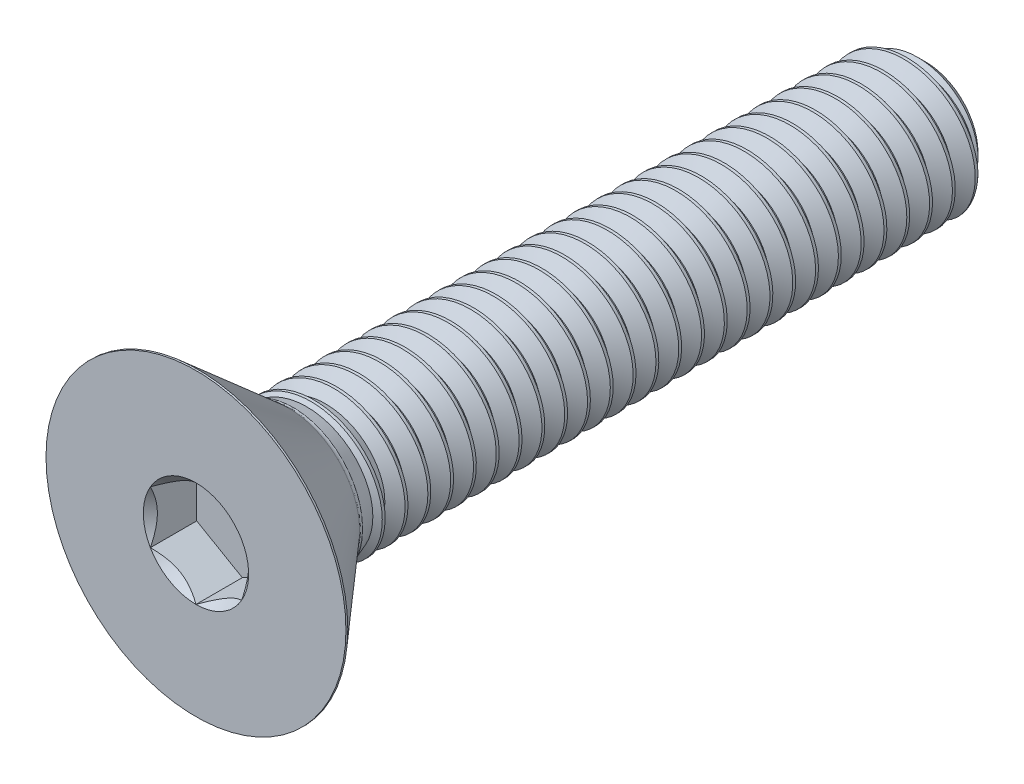
SolidWorks part; units mm, degrees
ref_plane "Front Plane" through (0, 0, 0) normal (0, 0, 1) x (1, 0, 0)
ref_plane "Top Plane" through (0, 0, 0) normal (0, 1, 0) x (1, 0, 0)
ref_plane "Right Plane" through (0, 0, 0) normal (1, 0, 0) x (0, 0, -1)
sketch "Sketch1" plane through (0, 0, 0) normal (1, 0, 0) x (0, 0, -1)
  line L0 (-12.7, 0) -> (12.7, 0) construction
  line L1 (-12.7, 0) -> (-12.7, 5.2197)
  line L2 (-12.7, 5.2197) -> (-12.6355, 5.2197)
  line L3 (-12.6355, 5.2197) -> (-9.4742, 2.4716)
  line L4 (-12.6355, -5.2197) -> (-9.4742, -2.4716)
  line L5 (12.7, 0) -> (12.7, 2.413)
  line L6 (12.7, 2.413) -> (-9.4742, 2.413)
  line L7 (12.1047, 2.413) -> (12.7, 1.8177)
  line L8 (12.6504, 2.4989) -> (13.0473, 1.8115) construction
  line L9 (13.0473, 1.8115) -> (13.4441, 2.4989) construction
  line L10 (13.4441, 2.4989) -> (12.6504, 2.4989) construction
  line L11 (12.6752, 2.456) -> (13.4193, 2.456)
  line L12 (13.4193, 2.456) -> (13.0969, 1.8974)
  line L13 (13.0969, 1.8974) -> (12.9977, 1.8974)
  line L14 (12.9977, 1.8974) -> (12.6752, 2.456)
  line L15 (13.0473, 1.8974) -> (13.0473, 1.8115) construction
  line L16 (12.7, 2.413) -> (13.3945, 2.413) construction
  line L17 (13.0473, 2.4989) -> (13.0473, 2.413) construction
  line L18 (12.7, -2.413) -> (-9.4742, -2.413)
  arc A0 (-9.4742, 2.4716) -> (-9.3174, 2.413) centre (-9.3174, 2.6521) ccw
  point P2 (0, 0)
  point P23 (-11.0871, 0)
  point P27 (13.0473, 2.456)
  point P30 (11.5094, -2.413)
  point P31 (-6.7075, 2.413)
  point P32 (10.0901, 2.413)
  point P33 (-9.4742, 5.2197)
  point P34 (-12.6355, -5.2197)
  point P37 (-6.0551, 2.413)
  dimension "Length" = 25.4
  dimension "Head Height" = 3.2258
  dimension "Head Diameter" = 10.4394
  dimension "Countersink Angle" = 82
  dimension "Screw Size Decimal Equivalent" = 4.826
  dimension "Pitch" = 0.7937
  dimension "D4" = 0.0992
  dimension "D3" = 45
  dimension "D5" = 0.5953
  dimension "D6" = 1.6129
  dimension "D1" = 1.1906
  dimension "D7" = 2.6098
  dimension "D8" = 2.6098
  dimension "D9" = 3.2623
  dimension "D2" = 0.0645
sketch "Sketch2" plane through (0, 0, 0) normal (0, 0, 1) x (1, 0, 0)
  line L1 (0, 1.8331) -> (-1.5875, 0.9165)
  line L2 (-1.5875, 0.9165) -> (-1.5875, -0.9165)
  line L3 (-1.5875, -0.9165) -> (0, -1.8331)
  line L4 (0, -1.8331) -> (1.5875, -0.9165)
  line L5 (1.5875, -0.9165) -> (1.5875, 0.9165)
  line L6 (1.5875, 0.9165) -> (0, 1.8331)
  circle A0 centre (0, 0) radius 1.5875 construction
  dimension "Drive Size" = 3.175
sketch "Sketch3" plane through (0, 0, 0) normal (1, 0, 0) x (0, 0, -1)
  line L0 (-12.6355, 5.2197) -> (-9.4742, 2.4716) construction
  line L1 (-12.7, 0) -> (-12.7, 5.2197) construction
  line L2 (-12.6355, 5.2197) -> (-9.4742, 2.4716)
  line L3 (-12.7, 0) -> (-12.7, 5.2197)
  line L4 (-12.7, 5.2197) -> (-12.6355, 5.2197) construction
  line L5 (-12.7, 5.2197) -> (-12.6355, 5.2197)
  line L6 (-9.3174, 2.413) -> (12.1047, 2.413)
  line L7 (12.1047, 2.413) -> (12.7, 1.8177)
  line L8 (12.7, 1.8177) -> (12.7, 0)
  line L9 (12.7, 0) -> (-12.7, 0)
  arc A0 (-9.4742, 2.4716) -> (-9.3174, 2.413) centre (-9.3174, 2.6521) ccw construction
  arc A1 (-9.4742, 2.4716) -> (-9.3174, 2.413) centre (-9.3174, 2.6521) ccw
revolve "Revolve1" add sketch "Sketch3" angle 360 about L9
sketch "Sketch4" plane through (0, 0, 12.7) normal (0, 0, 1) x (1, 0, 0)
  line L0 (1.5875, -0.9165) -> (1.5875, 0.9165) construction
  line L1 (0, -1.8331) -> (1.5875, -0.9165) construction
  line L2 (-1.5875, -0.9165) -> (0, -1.8331) construction
  line L3 (-1.5875, 0.9165) -> (-1.5875, -0.9165) construction
  line L4 (0, 1.8331) -> (-1.5875, 0.9165) construction
  line L5 (1.5875, 0.9165) -> (0, 1.8331) construction
  line L6 (1.5875, -0.9165) -> (1.5875, 0.9165)
  line L7 (0, -1.8331) -> (1.5875, -0.9165)
  line L8 (-1.5875, -0.9165) -> (0, -1.8331)
  line L9 (-1.5875, 0.9165) -> (-1.5875, -0.9165)
  line L10 (0, 1.8331) -> (-1.5875, 0.9165)
  line L11 (1.5875, 0.9165) -> (0, 1.8331)
sketch "Sketch5" plane through (0, 0, 12.7) normal (0, 0, 1) x (1, 0, 0)
  circle A0 centre (0, 0) radius 1.8331
extrude "Cut-Extrude1" cut sketch "Sketch5" against normal up to vertex (1.6129 mm away) draft 45 up to point (0, 0, 11.0871)
extrude "Cut-Extrude2" cut sketch "Sketch4" against normal up to vertex (1.6129 mm away) up to point (0, 0, 11.0871)
ref_plane "Plane1" through (0, 0, 9.3174) normal (0, 0, 1) x (1, 0, 0)
split "Split1" trim tools "Plane1" bodies to split 111 resulting bodies 105 106
sketch "Sketch6" plane through (0, 0, -12.7) normal (0, 0, -1) x (-1, 0, 0)
  circle A0 centre (0, 0) radius 2.413 construction
  circle A1 centre (0, 0) radius 2.413
curve "Helix/Spiral1" pitch 0.7937 height 25.4 turns 32
sketch "Sketch7" plane through (0, 0, 0) normal (1, 0, 0) x (0, 0, -1)
  line L0 (12.6752, 2.456) -> (13.4193, 2.456) construction
  line L1 (12.9977, 1.8974) -> (12.6752, 2.456) construction
  line L2 (13.0969, 1.8974) -> (12.9977, 1.8974) construction
  line L3 (13.4193, 2.456) -> (13.0969, 1.8974) construction
  line L4 (12.6752, 2.456) -> (13.4193, 2.456)
  line L5 (12.9977, 1.8974) -> (12.6752, 2.456)
  line L6 (13.0969, 1.8974) -> (12.9977, 1.8974)
  line L7 (13.4193, 2.456) -> (13.0969, 1.8974)
sweep "Cut-Sweep1" cut profiles "Sketch7" path "Helix/Spiral1"
sketch "Sketch8" plane through (0, 0, 9.3174) normal (0, 0, 1) x (1, 0, 0)
  circle A0 centre (0, 0) radius 2.413
extrude "Boss-Extrude1" add sketch "Sketch8" against normal up to next (22.0174 mm away) draft 20
equation "\"D4@Sketch1\" = \"Pitch@Sketch1\" / 8"
equation "\"D5@Sketch1\"=\"Pitch@Sketch1\"*0.75"
equation "\"D4@Helix/Spiral1\"=\"Pitch@Sketch1\""
equation "\"D3@Helix/Spiral1\"=\"Length@Sketch1\""
equation "\"D6@Sketch1\"=\"Head Height@Sketch1\"/2"
equation "\"D1@Sketch1\"=\"Pitch@Sketch1\"*1.5"
equation "\"D7@Sketch1\"=\"Head Diameter@Sketch1\"*0.25"
equation "\"D8@Sketch1\"=\"D7@Sketch1\""
equation "\"D9@Sketch1\"=1.25*\"D7@Sketch1\""
